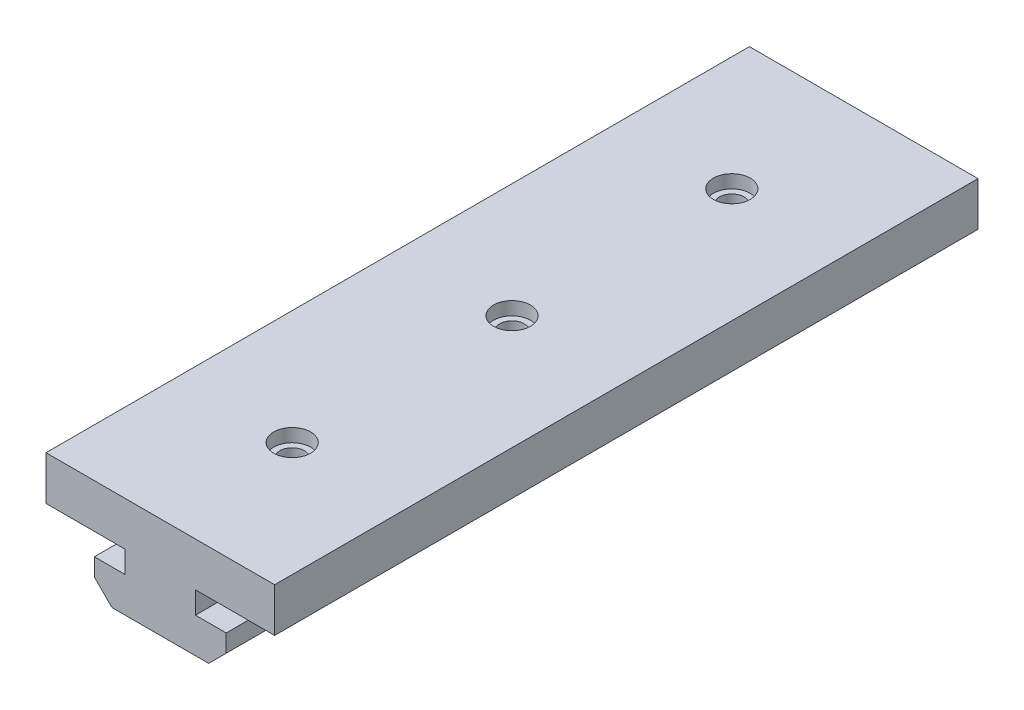
SolidWorks part; units mm, degrees
ref_plane "Front Plane" through (0, 0, 0) normal (0, 0, 1) x (1, 0, 0)
ref_plane "Top Plane" through (0, 0, 0) normal (0, 1, 0) x (1, 0, 0)
ref_plane "Right Plane" through (0, 0, 0) normal (1, 0, 0) x (0, 0, -1)
sketch "Sketch1" plane through (0, 0, 0) normal (0, 0, 1) x (1, 0, 0)
  line L28 (-13, 0) -> (-4, 0)
  line L29 (-4, 0) -> (-4, -2.5)
  line L30 (-4, -2.5) -> (-7.5, -2.5)
  line L31 (-7.5, -2.5) -> (-7.5, -4.5)
  line L32 (-7.5, -4.5) -> (-5.5, -6.5)
  line L33 (-5.5, -6.5) -> (5.5, -6.5)
  line L34 (5.5, -6.5) -> (7.5, -4.5)
  line L35 (7.5, -4.5) -> (7.5, -2.5)
  line L36 (7.5, -2.5) -> (4, -2.5)
  line L37 (4, -2.5) -> (4, 0)
  line L38 (4, 0) -> (13, 0)
  line L39 (13, 0) -> (13, 5)
  line L40 (13, 5) -> (-13, 5)
  line L41 (-13, 5) -> (-13, 0)
extrude "Extrude1" add sketch "Sketch1" along normal blind 80
sketch "Sketch2" plane through (0, 5, 0) normal (0, 1, 0) x (-1, 0, 0)
  line L0 (-13, 80) -> (13, 80) construction
  point P0 (0, 65)
  point P1 (0, 40)
  point P2 (0, 15)
  dimension "D1" = 15
  dimension "D2" = 40
  dimension "D3" = 65
hole_wizard "CBORE for M5 Hex Head Cap Screw1" positions "3DSketch1" profile "Sketch3" counterbore size "M5" standard "Ansi Metric" end condition through all
sketch3d "3DSketch1"
  point P0 (0, 5, 65)
  point P2 (0, 5, 40)
  point P4 (0, 5, 15)
sketch "Sketch3" plane through (0, 5, 65) normal (1, 0, 0) x (0, 0, 1)
  line L0 (0, 0) -> (0, 11.5)
  line L1 (0, 11.5) -> (1.4, 11.5)
  line L2 (0, 5.75) -> (1.7603, 5.75) construction
  line L3 (1.4, 10) -> (1.4, 1.5)
  line L4 (1.4, 1.5) -> (2.1, 1.5)
  line L5 (2.1, 1.5) -> (2.1, 0)
  line L6 (2.1, 10) -> (2.1, 11.5)
  line L7 (2.1, 0) -> (0, 0)
  line L8 (1.4, 10) -> (2.1, 10)
  line L9 (1.4, 11.5) -> (2.1, 11.5)
  line L11 (0, -6.35) -> (0, 107.95) construction
  dimension "Thru Hole Dia." = 2.8
  dimension "Thru Hole Depth" = 11.5
  dimension "C'Bore Dia." = 4.2
  dimension "C'Bore Depth" = 1.5
